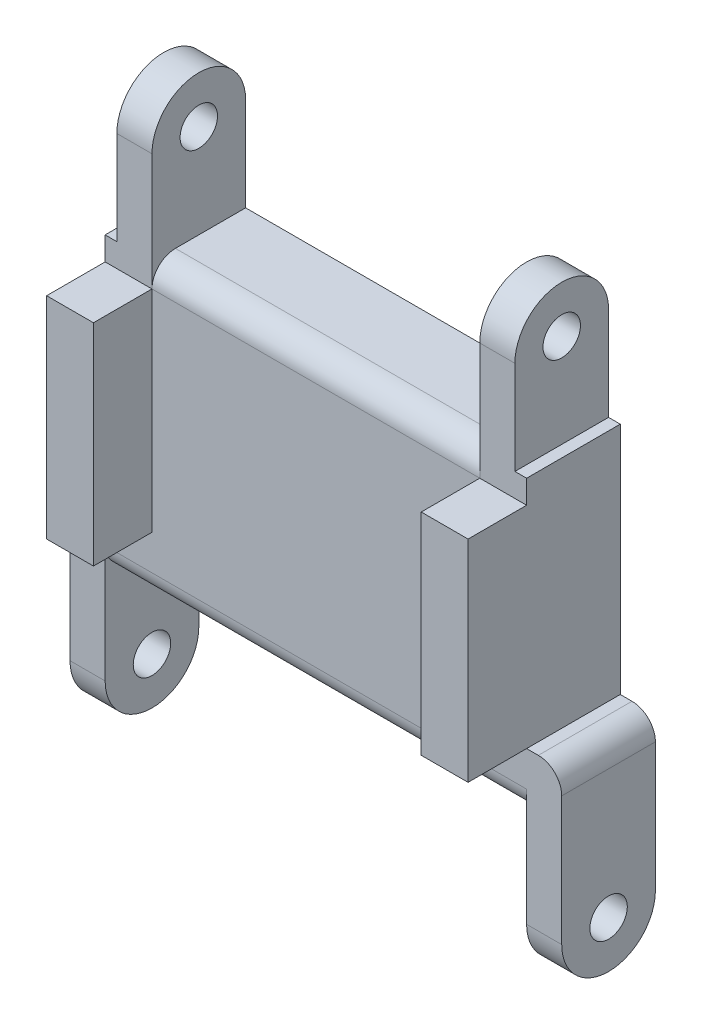
SolidWorks part; units mm, degrees
note: The reader was unsure of these and kept them because the rebuilt part matched: shared geometry of "Эскиз2<3>", "Эскиз4<3>".
ref_plane "Спереди" through (0, 0, 0) normal (0, 0, 1) x (1, 0, 0)
ref_plane "Сверху" through (0, 0, 0) normal (0, 1, 0) x (1, 0, 0)
ref_plane "Справа" through (0, 0, 0) normal (1, 0, 0) x (0, 0, -1)
sketch "Эскиз1" plane through (0, 0, 0) normal (0, 0, 1) x (1, 0, 0)
  line L0 (0, 0) -> (36, 0)
  line L1 (0, 0) -> (0, 25)
  line L2 (0, 25) -> (36, 25)
  line L3 (36, 25) -> (36, 0)
  dimension "D1" = 36
  dimension "D2" = 25
extrude "Бобышка-Вытянуть1" add sketch "Эскиз1" along normal blind 8
sketch "Эскиз2" plane through (36, 0, 0) normal (1, 0, 0) x (0, 0, -1)
  line L0 (-4, 0) -> (-4, 33) construction
  line L1 (-8, 0) -> (0, 0) construction
  line L2 (-8, 25) -> (-8, 33)
  line L3 (0, 25) -> (0, 33)
  line L4 (0, 0) -> (0, 25) construction
  line L6 (-8, 25) -> (0, 25) construction
  circle A2 centre (-4, 33) radius 4
  circle A3 centre (-4, 33) radius 1.6
  point P17 (-4, 28)
  point P18 (-4, 29.8463)
  dimension "D1" = 8
  dimension "D2" = 3.2
extrude "Бобышка-Вытянуть2" add sketch "Эскиз2" against normal blind 3 from offset 1 offset against normal yes
extrude "Бобышка-Вытянуть3" add sketch "Эскиз2<3>" along normal blind 3 from offset 35 offset against normal yes
sketch "Эскиз2<3>" plane through (36, 0, 0) normal (1, 0, 0) x (0, 0, -1) same geometry as "Эскиз2"
sketch "Эскиз4" plane through (0, 0, 0) normal (-1, 0, 0) x (0, 0, 1)
  line L0 (0, 25) -> (0, 0) construction
  line L1 (8, 0) -> (0, 0)
  line L2 (8, 0) -> (8, 5)
  line L3 (8, 5) -> (0, 5)
  line L4 (0, 0) -> (0, 5)
  line L5 (4, 25) -> (4, -8) construction
  line L6 (8, 0) -> (8, -8)
  line L7 (0, 0) -> (0, -8)
  line L8 (8, 25) -> (0, 25) construction
  circle A0 centre (4, -8) radius 4
  circle A3 centre (4, -8) radius 1.6
  point P9 (4, -6.8171)
  dimension "D3" = 8
  dimension "D2" = 3.2
  dimension "D1" = 5
extrude "Бобышка-Вытянуть4" add sketch "Эскиз4" along normal blind 3
fillet "Скругление2" radius 2 1 edges at (-3, 5, 4)
extrude "Бобышка-Вытянуть5" add sketch "Эскиз4<3>" against normal blind 3 from surface at -36
sketch "Эскиз4<3>" plane through (0, 0, 0) normal (-1, 0, 0) x (0, 0, 1) same geometry as "Эскиз4"
fillet "Скругление3" radius 2 1 edges at (39, 5, 4)
fillet "Скругление4" radius 2 1 edges at (18, 0, 8)
fillet "Скругление5" radius 2 1 edges at (18, 25, 8)
sketch "Эскиз5" plane through (0, 0, 8) normal (0, 0, 1) x (1, 0, 0)
  line L1 (4, 23) -> (0, 23)
  line L2 (4, 23) -> (4, 5)
  line L3 (4, 5) -> (0, 5)
  line L4 (0, 23) -> (0, 5)
  line L5 (32, 23) -> (36, 23)
  line L6 (32, 23) -> (32, 5)
  line L7 (32, 5) -> (36, 5)
  line L8 (36, 23) -> (36, 5)
extrude "Бобышка-Вытянуть6" add sketch "Эскиз5" along normal blind 5
